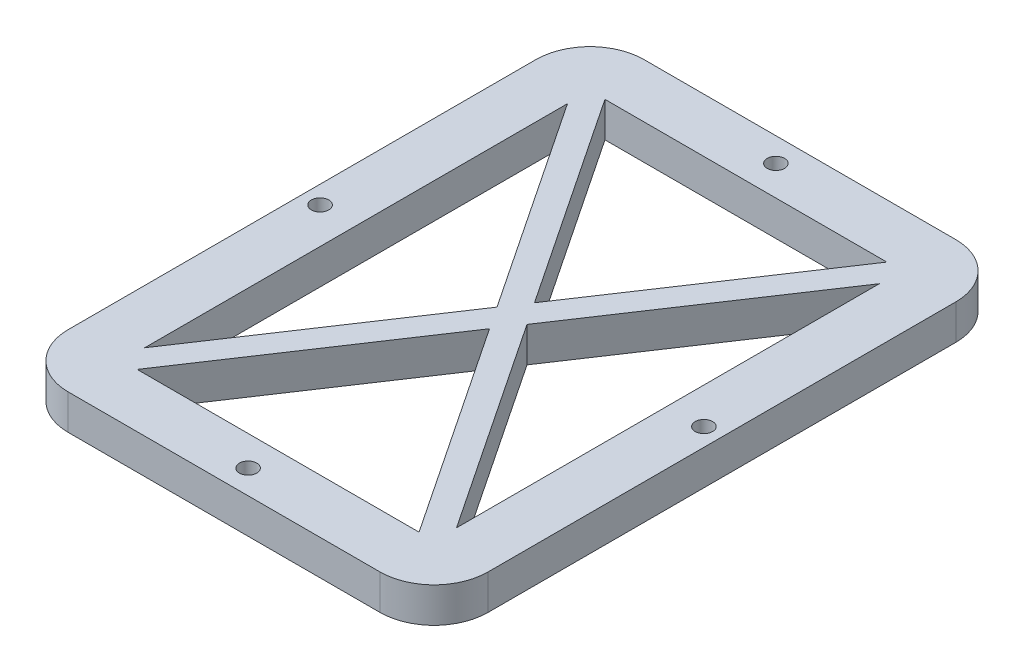
SolidWorks part; units mm, degrees
material "Acrylic (Medium-high impact)"
ref_plane "Front Plane" through (0, 0, 0) normal (0, 0, 1) x (1, 0, 0)
ref_plane "Top Plane" through (0, 0, 0) normal (0, 1, 0) x (1, 0, 0)
ref_plane "Right Plane" through (0, 0, 0) normal (1, 0, 0) x (0, 0, -1)
sketch "Sketch1" plane through (0, 0, 0) normal (0, 1, 0) x (1, 0, 0)
  line L0 (-35, 48) -> (-35, -48) construction
  line L1 (-35, 48) -> (35, 48) construction
  line L2 (-35, -48) -> (35, -48) construction
  line L3 (35, 48) -> (35, -48) construction
  line L4 (-28.5, -39) -> (-23.5, -39)
  line L5 (-28.5, -39) -> (23.5, 39)
  line L6 (-55, 0) -> (55, 0) construction
  line L7 (-74.55, 39) -> (60.5097, 39) construction
  line L8 (-26, 39) -> (26, 39)
  line L9 (-26, 39) -> (-26, -39)
  line L10 (-26, -39) -> (26, -39)
  line L11 (26, 39) -> (26, -39)
  line L12 (-26, 39) -> (26, -39) construction
  line L13 (-26, -39) -> (26, 39) construction
  line L14 (-71.5261, -39) -> (60.5097, -39) construction
  line L15 (-35, 39) -> (-35, -39)
  line L16 (-26, -996.6512) -> (-26, 49003.3488) construction
  line L17 (26, -1000) -> (26, 49000) construction
  line L18 (-26, 48) -> (26, 48)
  line L19 (35, 39) -> (35, -39)
  line L20 (-26, -48) -> (26, -48)
  line L21 (-62.4665, 0) -> (49937.5335, 0) construction
  line L22 (0, 0) -> (0, 50000) construction
  line L23 (-23.5, -39) -> (28.5, 39)
  line L24 (23.5, 39) -> (28.5, 39)
  line L25 (28.5, -39) -> (23.5, -39)
  line L26 (28.5, -39) -> (-23.5, 39)
  line L27 (23.5, -39) -> (-28.5, 39)
  line L28 (-23.5, 39) -> (-28.5, 39)
  arc A0 (-35, 39) -> (-26, 48) centre (-26, 39) cw
  arc A1 (26, 48) -> (35, 39) centre (26, 39) cw
  arc A2 (35, -39) -> (26, -48) centre (26, -39) cw
  arc A3 (-26, -48) -> (-35, -39) centre (-26, -39) cw
  circle A4 centre (0, 44) radius 1.45
  circle A5 centre (0, -44) radius 1.45
  circle A6 centre (-32, 0) radius 1.45
  circle A7 centre (32, 0) radius 1.45
  point P1 (0, 0)
  point P3 (0, 0)
  point P24 (26, 0)
  point P25 (35, 39)
  point P26 (35, -39)
  point P27 (-26, 48)
  point P28 (26, 48)
  point P34 (26, -48)
  point P35 (-26, -48)
  dimension "D6" = 5
  dimension "D7" = 2.9
  dimension "D8" = 2.5
  dimension "D10" = 32
  dimension "D11" = 2.9
  dimension "D1" = 96
  dimension "D2" = 70
  dimension "D3" = 78
  dimension "D4" = 52
extrude "Boss-Extrude1" add sketch "Sketch1" along normal blind 5.85 contours A3 L20 A2 L19 A1 L18 A0 L15 A7 A6 A5 A4 L28 L8 L24 L23 L11 L26 L25 L10 L4 L5 L9 L27 | L23 L27 L5 L9 L4 | L27 L5 L26 L8 L9 | L9 L28 L27 | L9 L5 L4 | L25 L26 L11 | L27 L10 L11 L26 L23 | L27 L23 L26 L5 | L26 L23 L11 L8 L5 | L24 L11 L23 region at (-26.8333, 0, 37.75) region at (-13.3152, 0, 19.9728) region at (-13.3152, 0, -19.9728) region at (0, 0, 0) region at (-26.8333, 0, -37.75) region at (13.3152, 0, 19.9728) region at (13.3152, 0, -19.9728) region at (26.8333, 0, 37.75) region at (26.8333, 0, -37.75) region at (-31.5238, 0, -44.5238)
